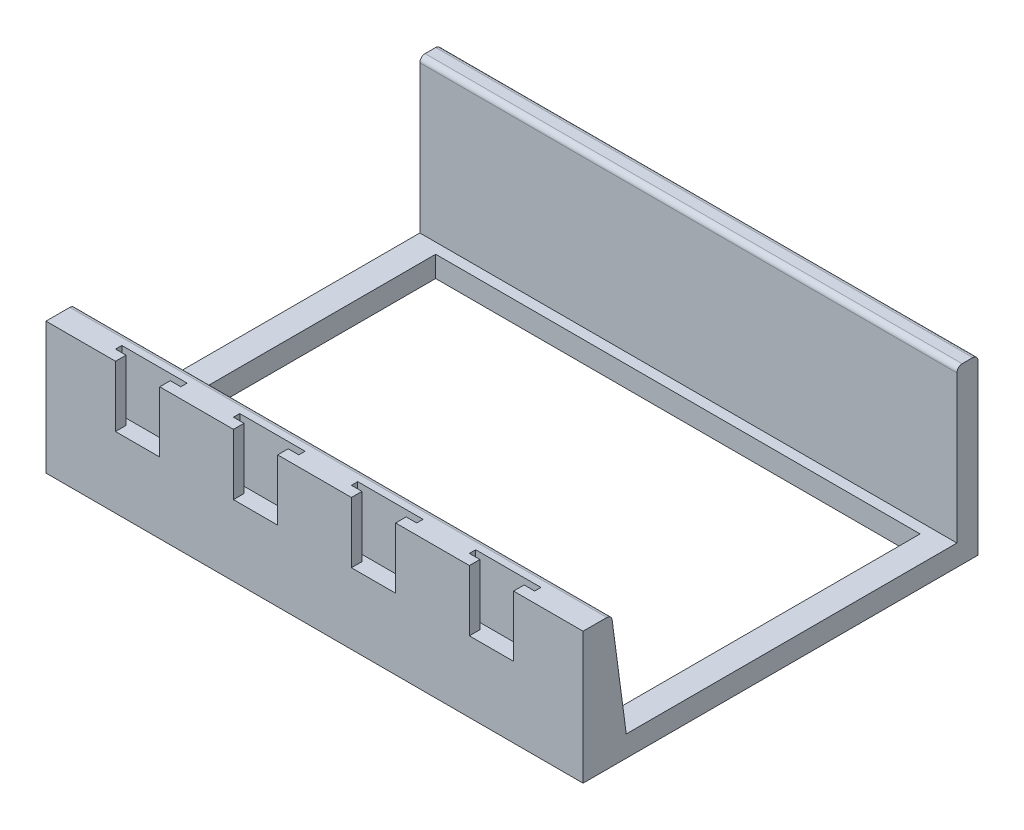
SolidWorks part; units mm, degrees
ref_plane "前视基准面" through (0, 0, 0) normal (0, 0, 1) x (1, 0, 0)
ref_plane "上视基准面" through (0, 0, 0) normal (0, 1, 0) x (1, 0, 0)
ref_plane "右视基准面" through (0, 0, 0) normal (1, 0, 0) x (0, 0, -1)
other "Configuration Table"
sketch "草图1" plane through (0, 0, 0) normal (0, 1, 0) x (1, 0, 0)
  line L1 (0, 0) -> (-102, 0)
  line L2 (0, 0) -> (0, 75)
  line L3 (0, 75) -> (-102, 75)
  line L4 (-102, 0) -> (-102, 75)
  dimension "D1" = 102
  dimension "D2" = 75
extrude "凸台-拉伸1" add sketch "草图1" along normal blind 25
sketch "草图2" plane through (0, 25, 0) normal (0, 1, 0) x (1, 0, 0)
  line L0 (-102, 75) -> (-102, 0) construction
  line L1 (-90.8, 2) -> (-88.8, 2)
  line L2 (-90.8, 2) -> (-90.8, 3.2)
  line L3 (-90.8, 3.2) -> (-78.4, 3.2)
  line L4 (-78.4, 2) -> (-78.4, 3.2)
  line L5 (-68.4, 2) -> (-66.4, 2)
  line L6 (-68.4, 2) -> (-68.4, 3.2)
  line L7 (-68.4, 3.2) -> (-56, 3.2)
  line L8 (-56, 2) -> (-56, 3.2)
  line L9 (-46, 3.2) -> (-33.6, 3.2)
  line L10 (-46, 3.2) -> (-46, 2)
  line L11 (-46, 2) -> (-44, 2)
  line L12 (-33.6, 3.2) -> (-33.6, 2)
  line L13 (-23.6, 3.2) -> (-11.2, 3.2)
  line L14 (-23.6, 3.2) -> (-23.6, 2)
  line L15 (-23.6, 2) -> (-21.6, 2)
  line L16 (-11.2, 3.2) -> (-11.2, 2)
  line L19 (-102, 0) -> (0, 0) construction
  line L20 (-13.2, 2) -> (-11.2, 2)
  line L22 (-88.8, 2) -> (-88.8, 0)
  line L23 (-88.8, 0) -> (-80.4, 0)
  line L24 (-80.4, 2) -> (-80.4, 0)
  line L26 (-66.4, 2) -> (-66.4, 0)
  line L27 (-66.4, 0) -> (-58, 0)
  line L28 (-58, 2) -> (-58, 0)
  line L30 (-44, 2) -> (-44, 0)
  line L31 (-44, 0) -> (-35.6, 0)
  line L32 (-35.6, 2) -> (-35.6, 0)
  line L34 (-21.6, 2) -> (-21.6, 0)
  line L35 (-21.6, 0) -> (-13.2, 0)
  line L36 (-13.2, 2) -> (-13.2, 0)
  line L37 (-35.6, 2) -> (-33.6, 2)
  line L38 (-58, 2) -> (-56, 2)
  line L39 (-80.4, 2) -> (-78.4, 2)
  point P16 (-68.4, 2.6)
  dimension "D1" = 12.4
  dimension "D2" = 12.4
  dimension "D3" = 12.4
  dimension "D4" = 12.4
  dimension "D5" = 10
  dimension "D6" = 10
  dimension "D7" = 10
  dimension "D8" = 11.2
  dimension "D9" = 2
  dimension "D10" = 2
  dimension "D11" = 2
  dimension "D12" = 2
  dimension "D13" = 1.2
  dimension "D14" = 1.2
  dimension "D15" = 1.2
  dimension "D16" = 1.2
  dimension "D17" = 2
  dimension "D18" = 2
  dimension "D19" = 2
  dimension "D20" = 2
  dimension "D21" = 2
  dimension "D22" = 2
  dimension "D23" = 2
  dimension "D24" = 2
extrude "切除-拉伸1" cut sketch "草图2" against normal offset from surface (11.56 mm away) 13.44 up to face at (-51, 0, -37.5)
sketch "草图3" plane through (0, 25, 0) normal (0, 1, 0) x (1, 0, 0)
  line L0 (0, 0) -> (0, 75) construction
  line L1 (-102, 75) -> (0, 75)
  line L2 (-102, 75) -> (-102, 8.2)
  line L3 (-102, 8.2) -> (0, 8.2)
  line L4 (0, 75) -> (0, 8.2)
  line L5 (-11.2, 3.2) -> (-23.6, 3.2) construction
  dimension "D1" = 5
extrude "切除-拉伸2" cut sketch "草图3" against normal blind 12
sketch "草图4" plane through (-102, 0, 0) normal (-1, 0, 0) x (0, 0, 1)
  line L6 (-75, 13) -> (-8.2, 13) construction
  line L7 (-71, 13) -> (-8.2, 13)
  line L8 (-71, 13) -> (-71, 4)
  line L9 (-71, 4) -> (-8.2, 4)
  line L10 (-8.2, 13) -> (-8.2, 4)
  line L11 (-75, 13) -> (-75, 0) construction
  line L12 (-75, 0) -> (0, 0) construction
  line L13 (-8.2, 13) -> (-8.2, 25) construction
  dimension "D1" = 4
  dimension "D2" = 4
extrude "切除-拉伸3" cut sketch "草图4" against normal through all
sketch "草图6" plane through (0, 13, 0) normal (0, 1, 0) x (1, 0, 0)
  line L4 (-102, 71) -> (0, 71)
  line L5 (0, 71) -> (0, 75)
  line L6 (0, 75) -> (-102, 75)
  line L7 (-102, 75) -> (-102, 71)
  line L8 (-102, 71) -> (0, 71)
  line L9 (0, 71) -> (0, 75)
  line L10 (0, 75) -> (-102, 75)
  line L11 (-102, 75) -> (-102, 71)
  dimension "D1" = 0
extrude "凸台-拉伸2" add sketch "草图6" along normal blind 20
sketch "草图7" plane through (0, 4, 0) normal (0, 1, 0) x (1, 0, 0)
  line L0 (0, 71) -> (0, 8.2) construction
  line L1 (-97, 69) -> (-5, 69)
  line L2 (-97, 69) -> (-97, 10.2)
  line L3 (-97, 10.2) -> (-5, 10.2)
  line L4 (-5, 69) -> (-5, 10.2)
  line L5 (-102, 71) -> (-102, 8.2) construction
  line L6 (-102, 71) -> (0, 71) construction
  line L7 (0, 8.2) -> (-102, 8.2) construction
  dimension "D1" = 5
  dimension "D2" = 5
  dimension "D3" = 2
  dimension "D4" = 2
extrude "切除-拉伸5" cut sketch "草图7" against normal blind 8
sketch "草图9" plane through (-102, 0, 0) normal (-1, 0, 0) x (0, 0, 1)
  line L0 (-8.2, 25) -> (-5.4, 25)
  line L2 (-5.4, 25) -> (-8.2, 4)
  line L3 (-8.2, 4) -> (-8.2, 25)
  dimension "D1" = 2.8
extrude "切除-拉伸6" cut sketch "草图9" against normal blind 108
fillet "圆角2" radius 1 3 edges at (-51, 33, -75) (-51, 33, -71) (-51, 25, -5.4)
